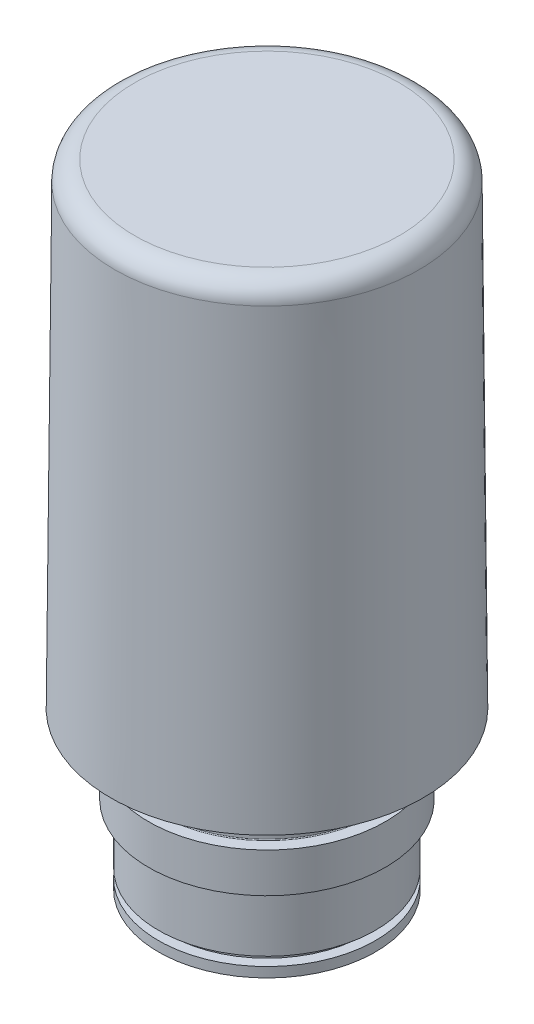
SolidWorks part; units mm, degrees
material "PVC Rigid"
ref_plane "Front Plane" through (0, 0, 0) normal (0, 0, 1) x (1, 0, 0)
ref_plane "Top Plane" through (0, 0, 0) normal (0, 1, 0) x (1, 0, 0)
ref_plane "Right Plane" through (0, 0, 0) normal (1, 0, 0) x (0, 0, -1)
sketch "Sketch1" plane through (0, 0, 0) normal (0, 0, 1) x (1, 0, 0)
  line L0 (0, 0) -> (0, 135.9298) construction
  line L1 (-13.97, 0) -> (-17.399, 0)
  line L2 (-17.399, 0) -> (-17.399, 1.5875)
  line L3 (-17.399, 1.5875) -> (-15.7607, 1.5875)
  line L4 (-15.7607, 1.5875) -> (-15.7607, 3.0099)
  line L5 (-15.7607, 3.0099) -> (-17.399, 3.0099)
  line L6 (-17.399, 3.0099) -> (-17.399, 12.5349)
  line L7 (-17.399, 12.5349) -> (-18.9738, 12.5349)
  line L8 (-18.9738, 12.5349) -> (-18.9738, 18.8849)
  line L9 (-18.9738, 18.8849) -> (-17.018, 18.8849)
  line L10 (-17.018, 18.8849) -> (-17.018, 22.4409)
  line L11 (-17.018, 22.4409) -> (-18.9738, 22.4409)
  line L12 (-18.9738, 22.4409) -> (-18.9738, 25.2349)
  line L13 (-18.3088, 101.4349) -> (0, 101.4349)
  line L14 (0, 101.4349) -> (0, 96.3549)
  line L15 (0, 96.3549) -> (-12.7, 96.3549)
  line L16 (-12.7, 96.3549) -> (-13.0099, 60.8469)
  line L17 (-18.9738, 25.2349) -> (-18.3088, 101.4349)
  line L18 (-19.05, 9.1791) -> (-19.05, 29.9268) construction
  line L19 (-19.0881, 9.1791) -> (-19.0881, 29.9268) construction
  line L20 (-17.018, 20.6629) -> (-18.2245, 20.6629) construction
  line L21 (-18.2245, 20.6629) -> (-18.3642, 20.6629) construction
  line L22 (-13.0099, 60.8469) -> (-13.97, 60.8469)
  line L23 (-13.97, 60.8469) -> (-13.97, 60.0269)
  line L24 (-13.97, 60.0269) -> (-14.7, 60.0269)
  line L25 (-14.7, 60.0269) -> (-14.7, 58.7269)
  line L26 (-14.7, 58.7269) -> (-13.97, 58.7269)
  line L27 (-13.97, 58.7269) -> (-13.97, 37.9349)
  line L28 (-17.399, 12.5349) -> (-13.97, 12.5349) construction
  line L29 (-13.97, 58.7269) -> (-13.97, 12.5349) construction
  line L30 (0, 95.8469) -> (-10, 95.8469) construction
  line L31 (-10, 95.8469) -> (-10, 60.8469) construction
  line L32 (-10, 60.8469) -> (-13.75, 60.8469) construction
  line L33 (-13.75, 60.8469) -> (-13.75, 60.0269) construction
  line L34 (-13.75, 60.0269) -> (-10.325, 60.0269) construction
  line L35 (-10.325, 60.0269) -> (-10.325, 57.1469) construction
  line L36 (-10.325, 57.1469) -> (-2.286, 57.1469) construction
  line L37 (-2.286, 57.1469) -> (-2.286, 53.0829) construction
  line L38 (-2.286, 53.0829) -> (0, 53.0829) construction
  line L39 (-13.97, 37.9349) -> (-14.7, 37.9349)
  line L40 (-14.7, 37.9349) -> (-14.7, 36.6349)
  line L41 (-14.7, 36.6349) -> (-13.97, 36.6349)
  line L42 (-13.97, 36.6349) -> (-13.97, 0)
  circle A0 centre (-18.3642, 20.6629) radius 1.3462 construction
  circle A1 centre (-18.2245, 20.6629) radius 1.27 construction
  point P29 (-19.4945, 20.6629)
  point P30 (-16.9545, 20.6629)
  point P31 (-19.7104, 20.6629)
  dimension "D4" = 2.54
  dimension "D5" = 2.6924
  dimension "D1" = 38.1
  dimension "D2" = 38.1762
  dimension "D3" = 0.0635
  dimension "D6" = 6.35
  dimension "D7" = 37.9476
  dimension "D8" = 17.399
  dimension "D9" = 34.036
  dimension "D10" = 0.4064
  dimension "D11" = 0.6223
  dimension "D12" = 5.08
  dimension "D13" = 12.7
  dimension "D14" = 22.225
  dimension "D15" = 1.5875
  dimension "D16" = 15.7607
  dimension "D17" = 1.4224
  dimension "D18" = 3.556
  dimension "D19" = 76.2
  dimension "D20" = 0.5
  dimension "D21" = 27.94
  dimension "D22" = 20
  dimension "D23" = 27.5
  dimension "D24" = 20.65
  dimension "D25" = 38.7
  dimension "D26" = 35
  dimension "D27" = 0.82
  dimension "D28" = 4.572
  dimension "D29" = 4.064
  dimension "D30" = 0.508
  dimension "D31" = 25.4
  dimension "D32" = 29.4
  dimension "D33" = 1.3
  dimension "D34" = 12.7
revolve "Revolve1" add sketch "Sketch1" angle 360 about L0
sketch "Sketch2" [suppressed] plane through (0, 0, 0) normal (0, 0, 1) x (1, 0, 0)
  line L0 (0, 0) -> (0, 123.6599) construction
  line L1 (0, 123.6599) -> (13.97, 123.6599)
  line L3 (13.97, 123.6599) -> (13.97, 0)
  line L4 (0, 0) -> (13.97, 0)
  line L5 (-17.4625, 0) -> (17.4625, 0) construction
  line L6 (17.1496, 123.6599) -> (-17.1496, 123.6599) construction
  line L7 (-13.97, 0) -> (13.97, 0) construction
  line L8 (0, 123.6599) -> (0, 0)
revolve "Revolve2" [suppressed] add sketch "Sketch2" angle 360 about L0
sketch "Sketch3" plane through (0, 101.4349, 0) normal (0, 1, 0) x (1, 0, 0)
  line L0 (0, 0) -> (18.9738, 0)
  line L1 (0, 0) -> (0, 18.9738)
  arc A0 (0, 18.9738) -> (18.9738, 0) centre (0, 0) ccw
  circle A1 centre (0, 0) radius 18.9738 construction
extrude "FEA Cut-Extrude1" [suppressed] cut sketch "Sketch3" against normal through all
ref_axis "Axis1" through (0, -6.183, 0) along (0, 1, 0)
fillet "Fillet2" radius 3.175 1 edges at (0, 96.3549, -12.7)
fillet "Fillet4" radius 0.127 2 edges at (0, 18.8849, -17.018) (0, 22.4409, -17.018)
fillet "HCE600 Fillet1" [suppressed] radius 3.175
sketch "Sketch4" plane through (0, 0, 0) normal (0, 0, 1) x (1, 0, 0)
  line L0 (0, 0) -> (0, 101.6111) construction
  line L1 (-18.3088, 101.4349) -> (-24.387, 101.4349)
  line L2 (-24.387, 101.4349) -> (-25.052, 25.2349)
  line L3 (-25.052, 25.2349) -> (-18.9738, 25.2349)
  line L4 (18.9738, 25.2349) -> (-18.9738, 25.2349) construction
  line L5 (-18.3088, 101.4349) -> (-18.9738, 25.2349) construction
  line L6 (-13.97, 48.3309) -> (-18.7719, 48.3728) construction
  line L8 (-24.8019, 53.8968) -> (-20, 53.8549) construction
  line L9 (-20, 53.8549) -> (-20, 25.2349) construction
  line L10 (-13.97, 58.7269) -> (-13.97, 37.9349) construction
  line L11 (-18.3088, 101.4349) -> (-18.9738, 25.2349)
  line L13 (-9.5526, 96.3549) -> (9.5526, 96.3549) construction
  dimension "D1" = 40
  dimension "D2" = 42.5
  dimension "D3" = 27.94
  dimension "D4" = 50.104
revolve "HC843E Revolve3" add sketch "Sketch4" angle 360 about L0
fillet "HC843E Fillet3" radius 3.175 1 edges at (0, 101.4349, -24.387)
